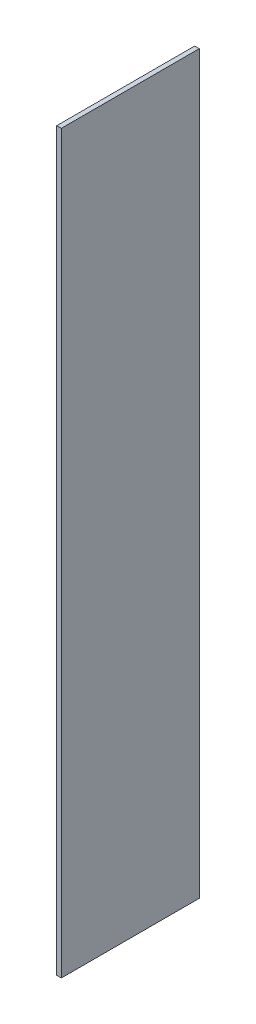
SolidWorks part; units mm, degrees
ref_plane "Front Plane" through (0, 0, 0) normal (0, 0, 1) x (1, 0, 0)
ref_plane "Top Plane" through (0, 0, 0) normal (0, 1, 0) x (1, 0, 0)
ref_plane "Right Plane" through (0, 0, 0) normal (1, 0, 0) x (0, 0, -1)
sketch "Sketch1" plane through (0, 0, 0) normal (0, 0, 1) x (1, 0, 0)
  line L1 (0, 0) -> (0.1, 0)
  line L2 (0, 0) -> (0, 16)
  line L3 (0, 16) -> (0.1, 16)
  line L4 (0.1, 0) -> (0.1, 16)
  dimension "D1" = 16
  dimension "D2" = 0.1
extrude "Boss-Extrude1" add sketch "Sketch1" along normal blind 3
equation "\"A.L\"= 0.07m"
equation "\"A.h\"= 0.007m"
equation "\"A.d\"= 0.003m"
equation "\"A.delta\"= 45.0001"
equation "\"A.w\"= 0.02m"
equation "\"A.v\"= 0.03m"
equation "\"A.s\"= 0.014m"
equation "\"A.t\"= 0.007m"
equation "\"B.L\"= 0.065m"
equation "\"B.h\"= 0.008m"
equation "\"B.s\"= 0.016m"
equation "\"B.t\"= 0.008m"
equation "\"C.h\"= 0.0065m"
equation "\"C.d\"= 0.003m"
equation "\"C.L\"= 0.05m"
equation "\"C.wmax\"= 0.005m"
equation "\"D.L\"= 0.06m"
equation "\"D.h\"= 0.008m"
equation "\"D.s\"= 0.012m"
equation "\"D.t\"= 0.008m"
equation "\"a_h\"= 0.0002m"
equation "\"a_d\"= 0.003m"
equation "\"a_L\"= 0.008m"
equation "\"b_h\"= 0.0004m"
equation "\"b_d\"= 0.003m"
equation "\"b_L\"= 0.007m"
equation "\"c_h\"= 0.0001m"
equation "\"c_d\"= 0.003m"
equation "\"c_L\"= 0.01m"
equation "\"d_h\"= 0.0001m"
equation "\"d_d\"= 0.003m"
equation "\"d_L\"= 0.01m"
equation "\"S.h\"= 0.015m"
equation "\"S.L\"= 0.09075m"
equation "\"D1@Sketch1\"=\"c_L\"+0.006"
equation "\"D2@Sketch1\"=\"c_h\""
equation "\"D1@Boss-Extrude1\"=\"c_d\""
